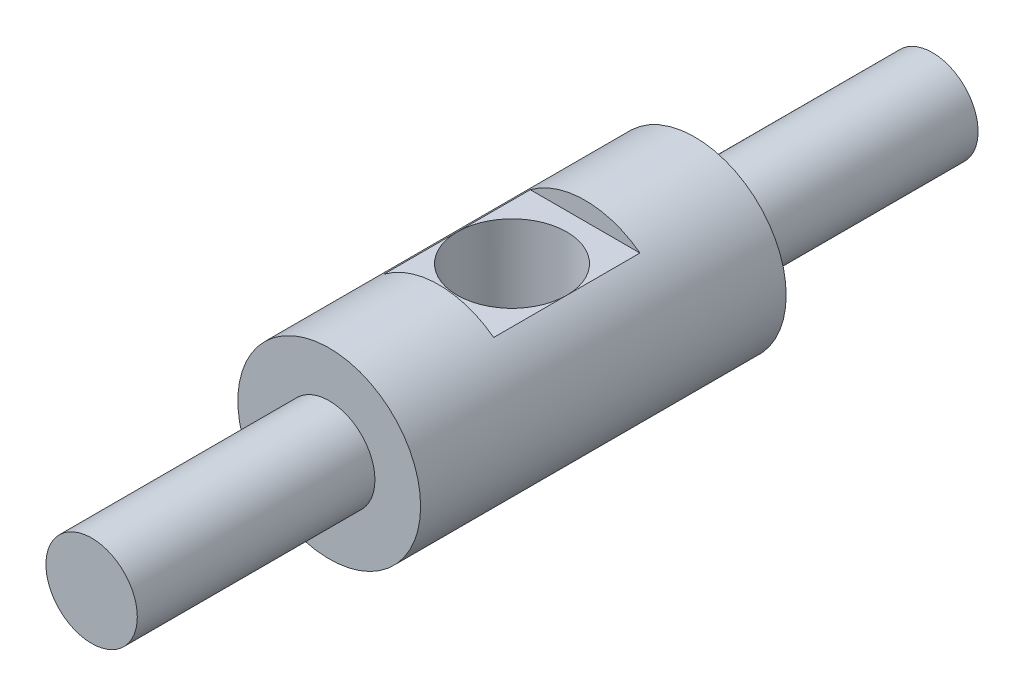
SolidWorks part; units mm, degrees
ref_plane "Ön Düzlem" through (0, 0, 0) normal (0, 0, 1) x (1, 0, 0)
ref_plane "Üst Düzlem" through (0, 0, 0) normal (0, 1, 0) x (1, 0, 0)
ref_plane "Sağ Düzlem" through (0, 0, 0) normal (1, 0, 0) x (0, 0, -1)
sketch "Çizim1" plane through (0, 0, 0) normal (0, 0, 1) x (1, 0, 0)
  circle A0 centre (0, 0) radius 25
extrude "Yükseklik-Ekstrüzyon1" add sketch "Çizim1" along normal blind 100
sketch "Çizim2" plane through (0, 0, 100) normal (0, 0, 1) x (1, 0, 0)
  circle A0 centre (0, 0) radius 12.5
extrude "Yükseklik-Ekstrüzyon2" add sketch "Çizim2" along normal blind 65
sketch "Çizim3" plane through (0, 0, 0) normal (0, 0, -1) x (-1, 0, 0)
  circle A0 centre (0, 0) radius 12.5
extrude "Yükseklik-Ekstrüzyon3" add sketch "Çizim3" along normal blind 65
sketch "Çizim4" plane through (0, 0, 0) normal (0, 1, 0) x (1, 0, 0)
  line L0 (0, 0) -> (0, -100)
  line L1 (-12.5, -100) -> (12.5, -100) construction
  circle A0 centre (0, -50) radius 15
extrude "Kes-Ekstrüzyon1" cut sketch "Çizim4" against normal blind 65 and the other way blind 65 contours L0 A0 | L0 A0 region at (6.3662, 0, 50) region at (-6.3662, 0, 50)
sketch "Çizim5" plane through (0, 0, 0) normal (0, 1, 0) x (1, 0, 0)
  line L2 (-20, -70) -> (20, -70)
  line L3 (-20, -70) -> (-20, -30)
  line L4 (-20, -30) -> (20, -30)
  line L5 (20, -70) -> (20, -30)
  dimension "D1" = 40
  dimension "D2" = 40
extrude "Kes-Ekstrüzyon2" cut sketch "Çizim5" along normal blind 10 from offset 20
